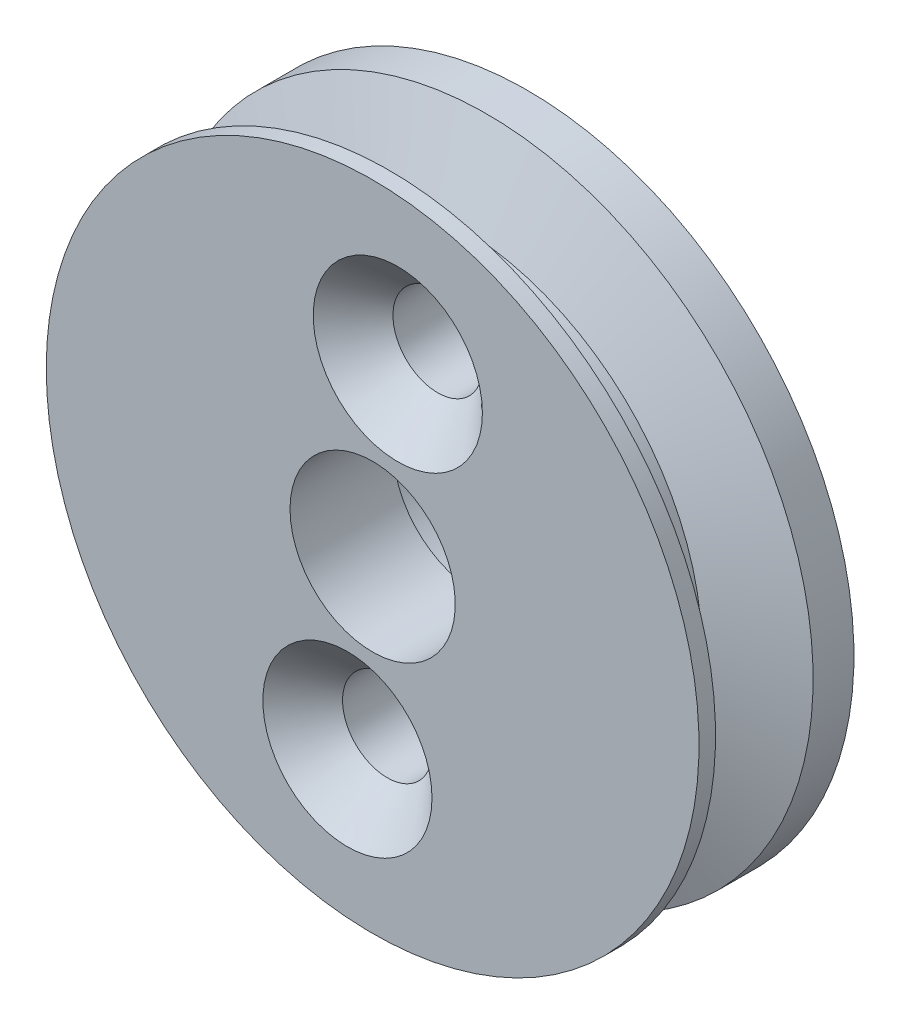
SolidWorks part; units mm, degrees
ref_plane "Front Plane" through (0, 0, 0) normal (0, 0, 1) x (1, 0, 0)
ref_plane "Top Plane" through (0, 0, 0) normal (0, 1, 0) x (1, 0, 0)
ref_plane "Right Plane" through (0, 0, 0) normal (1, 0, 0) x (0, 0, -1)
sketch "Sketch1" plane through (0, 0, 0) normal (1, 0, 0) x (0, 0, -1)
  line L0 (0, 0) -> (0, 7.1438) construction
  line L1 (0, 7.1438) -> (-3.175, 7.1437)
  line L2 (-3.175, 7.1437) -> (-3.175, 5.08)
  line L3 (-3.175, 5.08) -> (-9.525, 5.08)
  line L4 (-9.525, 5.08) -> (-9.525, 20.066)
  line L5 (-9.525, 20.066) -> (-8.509, 20.066)
  line L6 (-8.509, 20.066) -> (-6.6833, 15.05)
  line L7 (-6.6833, 15.05) -> (-4.3347, 15.05)
  line L8 (-4.3347, 15.05) -> (-2.509, 20.066)
  line L9 (-2.509, 20.066) -> (0, 20.066)
  line L10 (0, 20.066) -> (0, 7.1438)
  line L11 (0, 0) -> (-33.3615, 0) construction
  line L12 (-5.509, 15.05) -> (-5.509, 63.7674) construction
  line L13 (-6.3805, 19.05) -> (-2.5075, 19.05) construction
  dimension "D1" = 14.2875
  dimension "D2" = 3.175
  dimension "D3" = 10.16
  dimension "D4" = 40
  dimension "D5" = 6
  dimension "D6" = 4
  dimension "D7" = 1.016
  dimension "D8" = 19.05
  dimension "D9" = 9.525
  dimension "D10" = 1.016
revolve "Revolve1" add sketch "Sketch1" angle 360 about L11
hole_wizard "CSK for M5 Flat Head Machine Screw1" positions "Sketch2" profile "Sketch3" countersink size "M5" standard "ANSI Metric" end condition through all
sketch "Sketch2" plane through (0, 0, 9.525) normal (0, 0, 1) x (1, 0, 0)
  arc A1 (3.2605, 8.8707) -> (-0.6891, 9.4258) centre (1.5492, 11.0234) ccw construction
  arc A2 (-3.2605, -8.8707) -> (0.6891, -9.4258) centre (-1.5492, -11.0234) ccw construction
  point P0 (1.5492, 11.0234)
  point P2 (-1.5492, -11.0234)
  point P7 (0, 0)
  point P11 (0, 0)
  point P15 (0, 0)
sketch "Sketch3" plane through (1.5492, 11.0234, 9.525) normal (1, 0, 0) x (0, -1, 0)
  line L0 (0, 0) -> (0, 9.525)
  line L1 (0, 9.525) -> (2.75, 9.525)
  line L2 (2.75, 9.525) -> (2.75, 2.45)
  line L3 (2.75, 2.45) -> (5.2, 0)
  line L5 (5.2, 0) -> (0, 0)
  line L6 (-2.75, 2.45) -> (-5.2, 0) construction
  line L11 (0, -6.35) -> (0, 107.95) construction
  dimension "Thru Hole Dia." = 5.5
  dimension "Thru Hole Depth" = 9.525
  dimension "Near C'Sink Dia." = 10.4
  dimension "Near C'Sink Angle" = 90
equation "\"D1@Sketch1\"=9/16"
equation "\"D5@Sketch1\"=6mm"
equation "\"D6@Sketch1\"=4mm"
